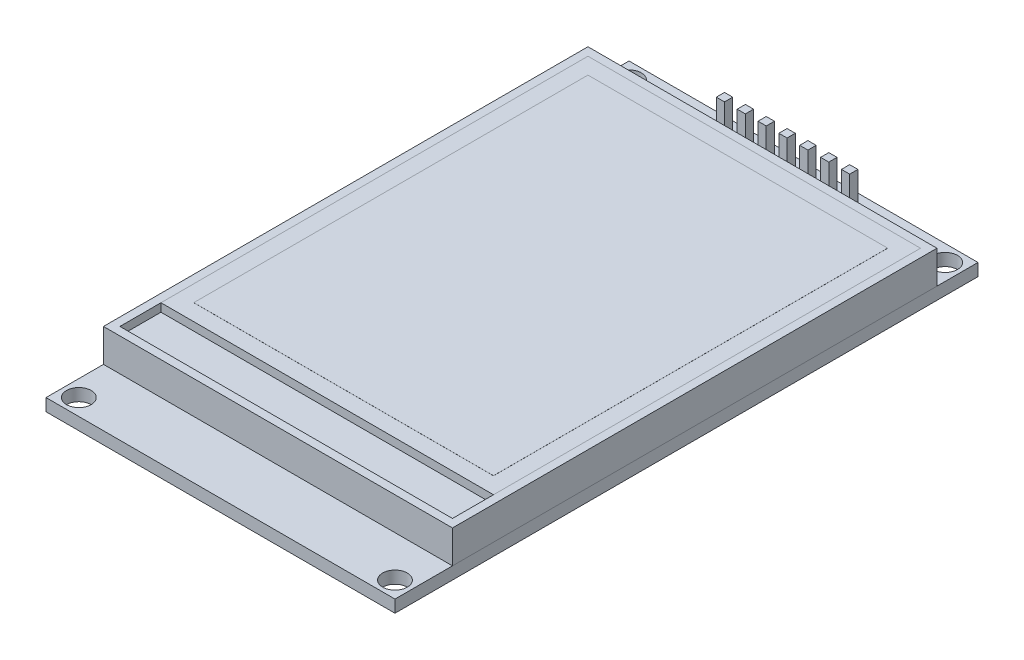
SolidWorks part; units mm, degrees
material "ABS"
ref_plane "Front Plane" through (0, 0, 0) normal (0, 0, 1) x (1, 0, 0)
ref_plane "Top Plane" through (0, 0, 0) normal (0, 1, 0) x (1, 0, 0)
ref_plane "Right Plane" through (0, 0, 0) normal (1, 0, 0) x (0, 0, -1)
sketch "Sketch1" plane through (0, 0, 0) normal (0, 1, 0) x (1, 0, 0)
  line L1 (-21.25, 35.5) -> (21.25, 35.5)
  line L2 (-21.25, 35.5) -> (-21.25, -35.5)
  line L3 (-21.25, -35.5) -> (21.25, -35.5)
  line L4 (21.25, 35.5) -> (21.25, -35.5)
  line L5 (0, -35.5) -> (0, 35.5) construction
  line L6 (-21.25, 0) -> (21.25, 0) construction
  point P0 (0, 0)
  dimension "D1" = 42.5
  dimension "D2" = 71
extrude "Boss-Extrude1" add sketch "Sketch1" along normal blind 1.5
sketch "Sketch7" plane through (0, 1.5, 0) normal (0, 1, 0) x (1, 0, 0)
  line L0 (-21.25, 35.5) -> (21.25, 35.5) construction
  line L1 (-21.25, 35.5) -> (-21.25, -35.5) construction
  circle A0 centre (-19.25, 33.5) radius 1.5
  dimension "D1" = 3
  dimension "D2" = 2
  dimension "D3" = 2
extrude "Cut-Extrude2" cut sketch "Sketch7" against normal through all
mirror "Mirror1" about plane through (0, 0, 0) normal (0, 0, 1) of "Cut-Extrude2" second plane through (0, 0, 0) second plane normal (1, 0, 0)
sketch "Sketch8" plane through (0, 1.5, 0) normal (0, 1, 0) x (1, 0, 0)
  line L0 (0, -10.821) -> (0, 10.821) construction
  line L1 (-0.5, 34) -> (0.5, 34)
  line L2 (-0.5, 34) -> (-0.5, 33)
  line L3 (-0.5, 33) -> (0.5, 33)
  line L4 (0.5, 34) -> (0.5, 33)
  line L5 (0, 33) -> (0, 34) construction
  line L6 (-0.5, 33.5) -> (0.5, 33.5) construction
  line L7 (-21.25, 35.5) -> (21.25, 35.5) construction
  point P0 (0, 33.5)
  dimension "D1" = 2
  dimension "D2" = 1
extrude "Boss-Extrude5" add sketch "Sketch8" along normal blind 4 and the other way blind 8
pattern_linear "LPattern1" count 4 spacing 2.54 along (1, 0, 0) count 4 spacing 2.54 along (-1, 0, 0) of "Boss-Extrude5" pattern seed only yes
sketch "Sketch2" plane through (0, 1.5, 0) normal (0, 1, 0) x (1, 0, 0)
  line L1 (-21.25, 30.5) -> (21.25, 30.5)
  line L2 (-21.25, 30.5) -> (-21.25, -28.5)
  line L3 (-21.25, -28.5) -> (21.25, -28.5)
  line L4 (21.25, 30.5) -> (21.25, -28.5)
  line L6 (-21.25, 35.5) -> (-21.25, -35.5) construction
  line L7 (21.25, 35.5) -> (21.25, -35.5) construction
  line L8 (-21.25, 35.5) -> (21.25, 35.5) construction
  line L9 (-21.25, -35.5) -> (21.25, -35.5) construction
  line L10 (-21.25, 1) -> (21.25, 1) construction
  point P4 (0, 1)
  dimension "D1" = 5
  dimension "D2" = 7
extrude "Boss-Extrude2" add sketch "Sketch2" along normal blind 4 separate body
sketch "Sketch3" plane through (0, 5.5, 0) normal (0, 1, 0) x (1, 0, 0)
  line L1 (-20.25, 29.5) -> (20.25, 29.5)
  line L2 (-20.25, 29.5) -> (-20.25, -27.5)
  line L3 (-20.25, -27.5) -> (20.25, -27.5)
  line L4 (20.25, 29.5) -> (20.25, -27.5)
  line L5 (0, -10.821) -> (0, 10.821) construction
  line L6 (-21.25, 30.5) -> (21.25, 30.5) construction
  line L7 (-21.25, 35.5) -> (-21.25, -35.5) construction
  line L9 (-21.25, 1) -> (21.25, 1) construction
  point P8 (0, 29.5)
  point P12 (-20.25, 1)
  dimension "D1" = 1
  dimension "D2" = 1
extrude "Cut-Extrude1" cut sketch "Sketch3" against normal through all
sketch "Sketch5" plane through (0, 1.5, 0) normal (0, 1, 0) x (1, 0, 0)
  line L4 (20.25, 29.5) -> (-20.25, 29.5)
  line L5 (20.25, -27.5) -> (20.25, 29.5)
  line L6 (-20.25, -27.5) -> (20.25, -27.5)
  line L7 (-20.25, 29.5) -> (-20.25, -27.5)
  line L8 (20.25, 29.5) -> (-20.25, 29.5)
  line L9 (20.25, -27.5) -> (20.25, 29.5)
  line L10 (-20.25, -27.5) -> (20.25, -27.5)
  line L11 (-20.25, 29.5) -> (-20.25, -27.5)
  dimension "D1" = 0
extrude "Boss-Extrude3" add sketch "Sketch5" along normal up to surface (4 mm away) separate body up to face at (0, 5.5, -1)
sketch "Sketch9" plane through (0, 5.5, 0) normal (0, 1, 0) x (1, 0, 0)
  line L0 (20.25, 29.5) -> (20.25, -27.5) construction
  line L1 (-20.25, -27.5) -> (20.25, -27.5)
  line L2 (-20.25, -27.5) -> (-20.25, -22.5)
  line L3 (-20.25, -22.5) -> (20.25, -22.5)
  line L4 (20.25, -27.5) -> (20.25, -22.5)
  dimension "D1" = 5
extrude "Cut-Extrude3" cut sketch "Sketch9" against normal blind 1
sketch "Sketch6" plane through (0, 5.5, 0) normal (0, 1, 0) x (1, 0, 0)
  line L0 (0, -10.821) -> (0, 10.821) construction
  line L1 (-18.25, 27.5) -> (18.25, 27.5)
  line L2 (-18.25, 27.5) -> (-18.25, -20.5)
  line L3 (-18.25, -20.5) -> (18.25, -20.5)
  line L4 (18.25, 27.5) -> (18.25, -20.5)
  line L5 (21.25, 35.5) -> (-21.25, 35.5) construction
  line L6 (-20.25, 29.5) -> (20.25, 29.5) construction
  line L7 (-20.25, 29.5) -> (-20.25, -27.5) construction
  line L12 (20.25, 29.5) -> (-20.25, 29.5) construction
  line L13 (-20.25, 29.5) -> (-20.25, -27.5) construction
  line L14 (-21.25, 35.5) -> (-21.25, -35.5) construction
  line L15 (-20.25, -22.5) -> (20.25, -22.5) construction
  line L16 (20.25, -22.5) -> (-20.25, -22.5) construction
  line L17 (-21.25, -35.5) -> (21.25, -35.5) construction
  point P4 (0, 27.5)
  dimension "D1" = 2
  dimension "D2" = 2
  dimension "D3" = 2
  dimension "D4" = 13
  dimension "D7" = 6
  dimension "D8" = 1
extrude "Boss-Extrude4" add sketch "Sketch6" along normal blind 0.01
